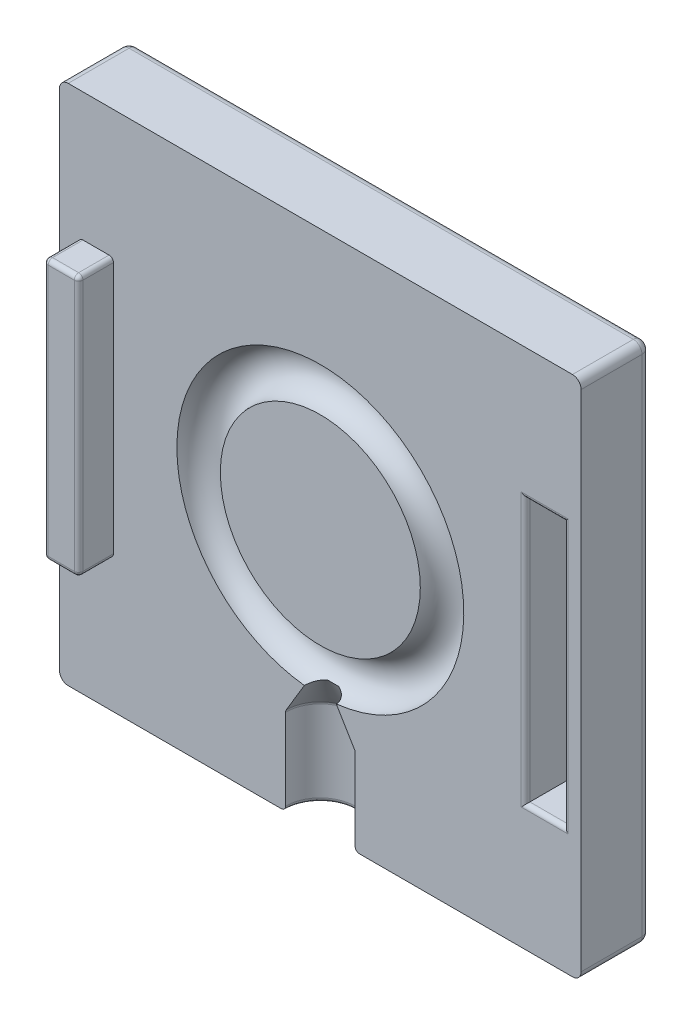
SolidWorks part; units mm, degrees
ref_plane "Front Plane" through (0, 0, 0) normal (0, 0, 1) x (1, 0, 0)
ref_plane "Top Plane" through (0, 0, 0) normal (0, 1, 0) x (1, 0, 0)
ref_plane "Right Plane" through (0, 0, 0) normal (1, 0, 0) x (0, 0, -1)
sketch "Sketch1" plane through (0, 0, 0) normal (0, 0, 1) x (1, 0, 0)
  line L1 (15, -15) -> (-15, -15)
  line L2 (15, -15) -> (15, 15)
  line L3 (15, 15) -> (-15, 15)
  line L4 (-15, -15) -> (-15, 15)
  line L5 (15, -15) -> (-15, 15) construction
  line L6 (15, 15) -> (-15, -15) construction
  point P0 (0, 0)
  dimension "D1" = 30
  dimension "D2" = 30
extrude "Boss-Extrude1" add sketch "Sketch1" along normal blind 4
sketch "Sketch4" plane through (0, 0, 0) normal (0, 1, 0) x (1, 0, 0)
  line L0 (15, -4) -> (-15, -4) construction
  line L1 (0, 0) -> (0, -8.7634) construction
  circle A0 centre (7, -4) radius 1.25
  point P7 (5.75, -4)
  point P8 (8.25, -4)
  dimension "D1" = 5.75
  dimension "D2" = 2.5
revolve "Cut-Revolve1" cut sketch "Sketch4" angle 360 about L1
ref_plane "Plane1" through (0, -8, 0) normal (0, 1, 0) x (1, 0, 0)
sketch "Sketch9" plane through (0, 0, 0) normal (1, 0, 0) x (0, 0, -1)
  line L0 (-4, -8) -> (-4, -15) construction
  line L1 (3.3, -8) -> (-3.3, -8) construction
  line L2 (-4, -15) -> (-4, 15) construction
  line L3 (-4, -8) -> (-4.8, -8)
  line L4 (-6, -10) -> (-4.8, -8)
  line L5 (-6, -15) -> (-4, -15)
  line L6 (-4, -8) -> (-4, -15)
  line L7 (-4, 15) -> (-4, -15) construction
  line L8 (-6, -15) -> (-6, -10)
  dimension "D1" = 2
  dimension "D2" = 0.8
  dimension "D3" = 5
revolve "Cut-Revolve2" cut sketch "Sketch9" angle 360 about L0
sketch "Sketch7" plane through (0, 0, 4) normal (0, 0, 1) x (1, 0, 0)
  line L0 (-15, 15) -> (-15, -15) construction
  line L1 (-11.9, 7.6214) -> (-13.9, 7.6214)
  line L2 (-11.9, 7.6214) -> (-11.9, -7.3786)
  line L3 (-11.9, -7.3786) -> (-13.9, -7.3786)
  line L4 (-13.9, 7.6214) -> (-13.9, -7.3786)
  line L5 (-11.9, 7.6214) -> (-13.9, -7.3786) construction
  line L6 (-11.9, -7.3786) -> (-13.9, 7.6214) construction
  point P0 (-12.9, 0.1214)
  dimension "D1" = 15
  dimension "D2" = 2
  dimension "D3" = 1.1
extrude "Boss-Extrude2" add sketch "Sketch7" along normal blind 2
sketch "Sketch8" plane through (0, 0, 4) normal (0, 0, 1) x (1, 0, 0)
  line L0 (15, -15) -> (15, 15) construction
  line L1 (14, 7.4342) -> (11.8, 7.4342)
  line L2 (14, 7.4342) -> (14, -7.7658)
  line L3 (14, -7.7658) -> (11.8, -7.7658)
  line L4 (11.8, 7.4342) -> (11.8, -7.7658)
  line L5 (14, 7.4342) -> (11.8, -7.7658) construction
  line L6 (14, -7.7658) -> (11.8, 7.4342) construction
  point P0 (12.9, -0.1658)
  dimension "D1" = 15.2
  dimension "D2" = 2.2
  dimension "D3" = 1
extrude "Cut-Extrude2" cut sketch "Sketch8" against normal blind 2.5
fillet "Fillet1" radius 0.25 4 edges at (-12.9, 7.6214, 6) (-11.9, 0.1214, 6) (-12.9, -7.3786, 6) (-13.9, 0.1214, 6)
fillet "Fillet2" radius 0.25 8 edges at (-11.9732, 7.5482, 5.9268) (-13.8268, 7.5482, 5.9268) (-13.8268, -7.3053, 5.9268) (-11.9732, -7.3053, 5.9268) (-11.9, 7.6214, 4.875) (-13.9, 7.6214, 4.875) (-13.9, -7.3786, 4.875) (-11.9, -7.3786, 4.875)
fillet "Fillet3" radius 0.25 4 edges at (12.9, -7.7658, 4) (14, -0.1658, 4) (12.9, 7.4342, 4) (11.8, -0.1658, 4)
fillet "Fillet5" radius 0.5 4 edges at (0, -15, 0) (15, 0, 0) (0, 15, 0) (-15, 0, 0)
fillet "Fillet6" radius 0.5 8 edges at (-14.8536, -14.8536, 0.1464) (-14.8536, 14.8536, 0.1464) (14.8536, 14.8536, 0.1464) (14.8536, -14.8536, 0.1464) (-15, -15, 2.25) (-15, 15, 2.25) (15, 15, 2.25) (15, -15, 2.25)
fillet "Fillet7" radius 0.25 2 edges at (0, -10, 2) (0, -15, 2)
